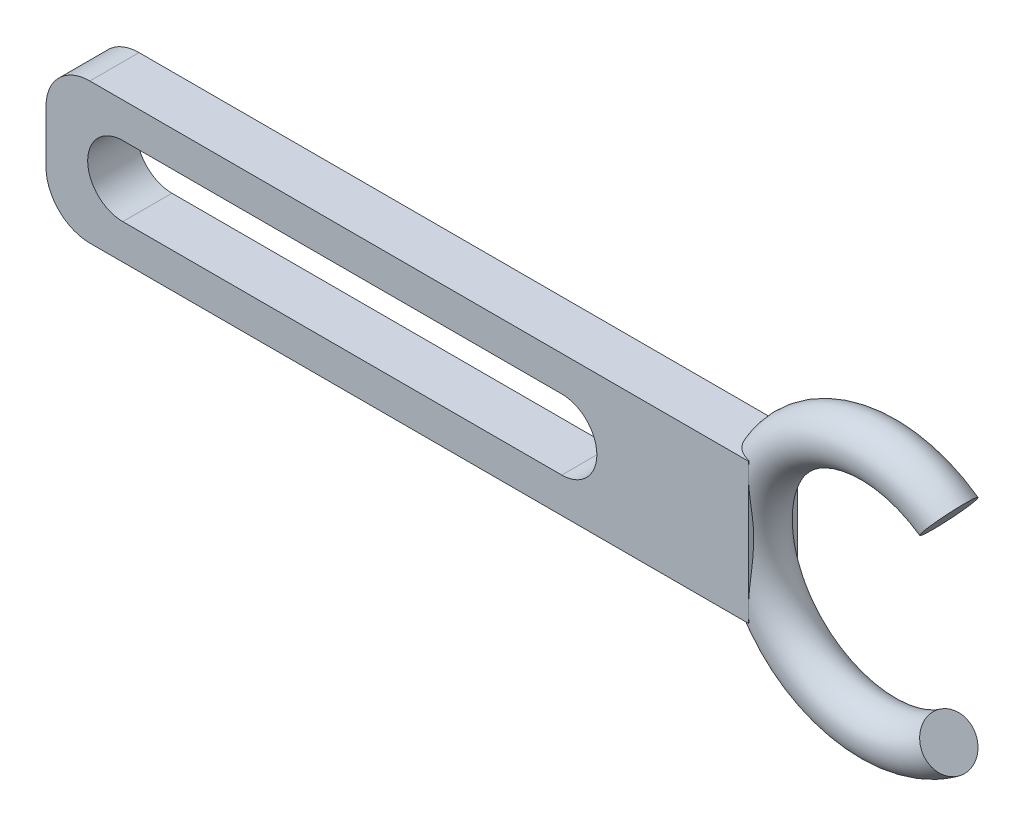
SolidWorks part; units mm, degrees
material "ABS"
ref_plane "Plano frontal" through (0, 0, 0) normal (0, 0, 1) x (1, 0, 0)
ref_plane "Plano superior" through (0, 0, 0) normal (0, 1, 0) x (1, 0, 0)
ref_plane "Plano direito" through (0, 0, 0) normal (1, 0, 0) x (0, 0, -1)
sketch "Esboço2" plane through (0, 0, 0) normal (0, 1, 0) x (1, 0, 0)
  line L0 (0, 0) -> (0, 8.2994) construction
  circle A0 centre (13.75, 0) radius 2.8
  dimension "D1" = 13.75
revolve "Revolução1" add sketch "Esboço2" angle 360 about L0 other way angle 360
sketch "Esboço3" plane through (0, 0, 0) normal (0, 0, 1) x (1, 0, 0)
  line L0 (-1.2027, 0) -> (18.8767, 24.2478)
  line L1 (3.08, 0) -> (-3.08, 0) construction
  line L2 (-6.1474, 0) -> (26.9282, 0) construction
  line L3 (-1.2027, 0) -> (18.8767, -24.2478)
  line L4 (18.8767, 24.2478) -> (18.8767, -24.2478)
extrude "Corte-extrusão1" cut sketch "Esboço3" against normal blind 10 and the other way blind 10
sketch "Esboço5" plane through (0, 0, 0) normal (1, 0, 0) x (0, 0, -1)
  line L0 (2.8, -13.75) -> (2.8, 13.75) construction
  line L1 (-2.8, -8) -> (2.8, -8)
  line L2 (-2.8, -8) -> (-2.8, 8)
  line L3 (-2.8, 8) -> (2.8, 8)
  line L4 (2.8, -8) -> (2.8, 8)
  line L5 (-2.8, -8) -> (2.8, 8) construction
  line L6 (-2.8, 8) -> (2.8, -8) construction
  point P0 (0, 0)
extrude "Ressalto-extrusão1" add sketch "Esboço5" against normal blind 80 from offset 12 offset against normal yes
fillet "Filete1" radius 5 2 edges at (-92, 8, 0) (-92, -8, 0)
sketch "Esboço7" plane through (0, 0, -2.8) normal (0, 0, -1) x (-1, 0, 0)
  line L0 (3.08, 0) -> (-3.08, 0) construction
  line L1 (33.2543, 4) -> (83.2543, 4)
  line L2 (83.2543, -4) -> (33.2543, -4)
  arc A0 (83.2543, -4) -> (83.2543, 4) centre (83.2543, 0) ccw
  arc A1 (33.2543, 4) -> (33.2543, -4) centre (33.2543, 0) ccw
  dimension "D1" = 50
  dimension "D2" = 8
extrude "Corte-extrusão2" cut sketch "Esboço7" against normal blind 19
